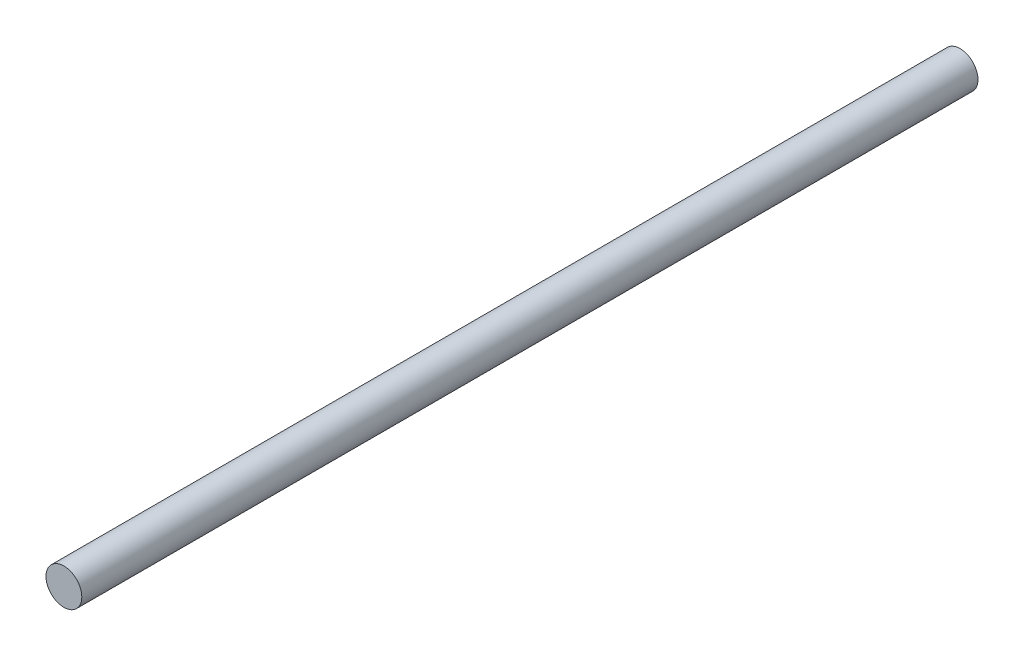
SolidWorks part; units mm, degrees
ref_plane "Спереди" through (0, 0, 0) normal (0, 0, 1) x (1, 0, 0)
ref_plane "Сверху" through (0, 0, 0) normal (0, 1, 0) x (1, 0, 0)
ref_plane "Справа" through (0, 0, 0) normal (1, 0, 0) x (0, 0, -1)
sketch "Эскиз1" plane through (0, 0, 0) normal (0, 0, 1) x (1, 0, 0)
  circle A0 centre (0, 0) radius 2
  dimension "D1" = 4
extrude "Шпилька на тяги" add sketch "Эскиз1" along normal blind 100
